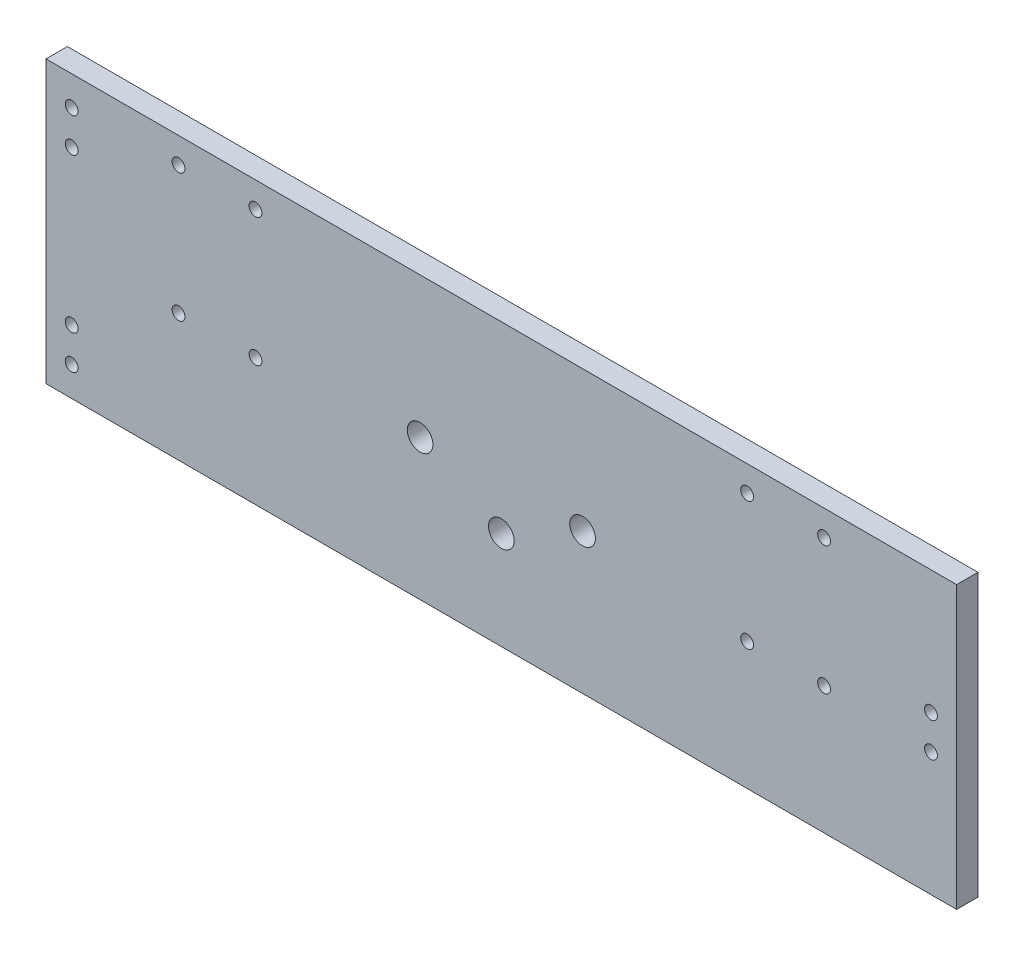
SolidWorks part; units mm, degrees
ref_plane "前视基准面" through (0, 0, 0) normal (0, 0, 1) x (1, 0, 0)
ref_plane "上视基准面" through (0, 0, 0) normal (0, 1, 0) x (1, 0, 0)
ref_plane "右视基准面" through (0, 0, 0) normal (1, 0, 0) x (0, 0, -1)
sketch "草图3" plane through (0, 0, 0) normal (0, 0, 1) x (1, 0, 0)
  line L1 (106.5, -32.9) -> (-106.5, -32.9)
  line L2 (106.5, -32.9) -> (106.5, 32.9)
  line L3 (106.5, 32.9) -> (-106.5, 32.9)
  line L4 (-106.5, -32.9) -> (-106.5, 32.9)
  line L5 (106.5, -32.9) -> (-106.5, 32.9) construction
  line L6 (106.5, 32.9) -> (-106.5, -32.9) construction
  line L7 (125, -27.9) -> (40, -27.9) construction
  line L8 (125, -27.9) -> (125, 27.9) construction
  line L9 (125, 27.9) -> (40, 27.9) construction
  line L10 (40, -27.9) -> (40, 27.9) construction
  line L11 (125, -27.9) -> (40, 27.9) construction
  line L12 (125, 27.9) -> (40, -27.9) construction
  point P0 (0, 0)
  point P6 (82.5, 0)
  point P19 (0, 0)
  dimension "D1" = 213
  dimension "D2" = 55.8
  dimension "D3" = 5
  dimension "D4" = 5
  dimension "D5" = 85
  dimension "D6" = 40
  dimension "D18" = 0
  dimension "D20" = 0
extrude "凸台-拉伸2" add sketch "草图3" along normal blind 5
sketch "草图4" plane through (0, 0, 5) normal (0, 0, 1) x (1, 0, 0)
  line L0 (-106.5, -32.9) -> (106.5, -32.9) construction
  line L2 (66.5, 32.9) -> (66.5, -32.9) construction
  line L3 (0, 32.9) -> (0, -32.9) construction
  line L4 (106.5, 32.9) -> (-106.5, 32.9) construction
  line L5 (106.5, -32.9) -> (106.5, 32.9) construction
  line L6 (-66.5, 32.9) -> (-66.5, -32.9) construction
  circle A0 centre (75.5, 26.9) radius 1.5
  circle A1 centre (75.5, -3.1) radius 1.5
  circle A2 centre (-75.5, -3.1) radius 1.5
  circle A3 centre (-75.5, 26.9) radius 1.5
  circle A4 centre (57.5, -3.1) radius 1.5
  circle A5 centre (57.5, 26.9) radius 1.5
  circle A6 centre (-57.5, -3.1) radius 1.5
  circle A7 centre (-57.5, 26.9) radius 1.5
  dimension "D1" = 3
  dimension "D2" = 3
  dimension "D3" = 40
  dimension "D4" = 30
  dimension "D5" = 6
  dimension "D6" = 18
extrude "切除-拉伸1" cut sketch "草图4" against normal blind 5
sketch "草图5" plane through (0, 0, 5) normal (0, 0, 1) x (1, 0, 0)
  line L0 (106.5, 32.9) -> (-106.5, 32.9) construction
  line L1 (-106.5, 32.9) -> (-106.5, -32.9) construction
  line L2 (-100.5, 26) -> (-100.5, 4) construction
  line L3 (-106.5, -32.9) -> (106.5, -32.9) construction
  line L4 (0, 32.9) -> (0, -32.9) construction
  circle A0 centre (-100.5, 26) radius 1.5
  circle A12 centre (-100.5, 18) radius 1.5
  circle A13 centre (-100.5, 4) radius 1.5
  circle A14 centre (-100.5, -4) radius 1.5
  circle A15 centre (-100.5, -18) radius 1.5
  circle A16 centre (-100.5, -26) radius 1.5
  circle A17 centre (100.5, -26) radius 1.5
  circle A18 centre (100.5, -18) radius 1.5
  circle A19 centre (100.5, -4) radius 1.5
  circle A20 centre (100.5, 4) radius 1.5
  circle A21 centre (100.5, 18) radius 1.5
  circle A22 centre (100.5, 26) radius 1.5
  dimension "D1" = 3
  dimension "D4" = 3
  dimension "D2" = 6.9
  dimension "D3" = 6
  dimension "D5" = 8
  dimension "D6" = 3
  dimension "D7" = 22
extrude "切除-拉伸2" cut sketch "草图5" against normal blind 5 contours A0 | A12 | A20 | A19 | A15 | A16 region at (-100.5, 26, 5) region at (-100.5, 18, 5) region at (-100.5, -18, 5) region at (-100.5, -26, 5) region at (100.5, -4, 5) region at (100.5, 4, 5)
sketch "草图6" plane through (0, 0, 5) normal (0, 0, 1) x (1, 0, 0)
  circle A0 centre (19, 0) radius 3
  circle A1 centre (-19, 0) radius 3
  circle A2 centre (0, -10) radius 3
  point P7 (0, 0)
  point P9 (-0.1547, 0.4531)
  dimension "D3" = 6
  dimension "D4" = 6
  dimension "D5" = 6
  dimension "D1" = 19
  dimension "D2" = 19
  dimension "D6" = 10
extrude "切除-拉伸3" cut sketch "草图6" against normal blind 10
